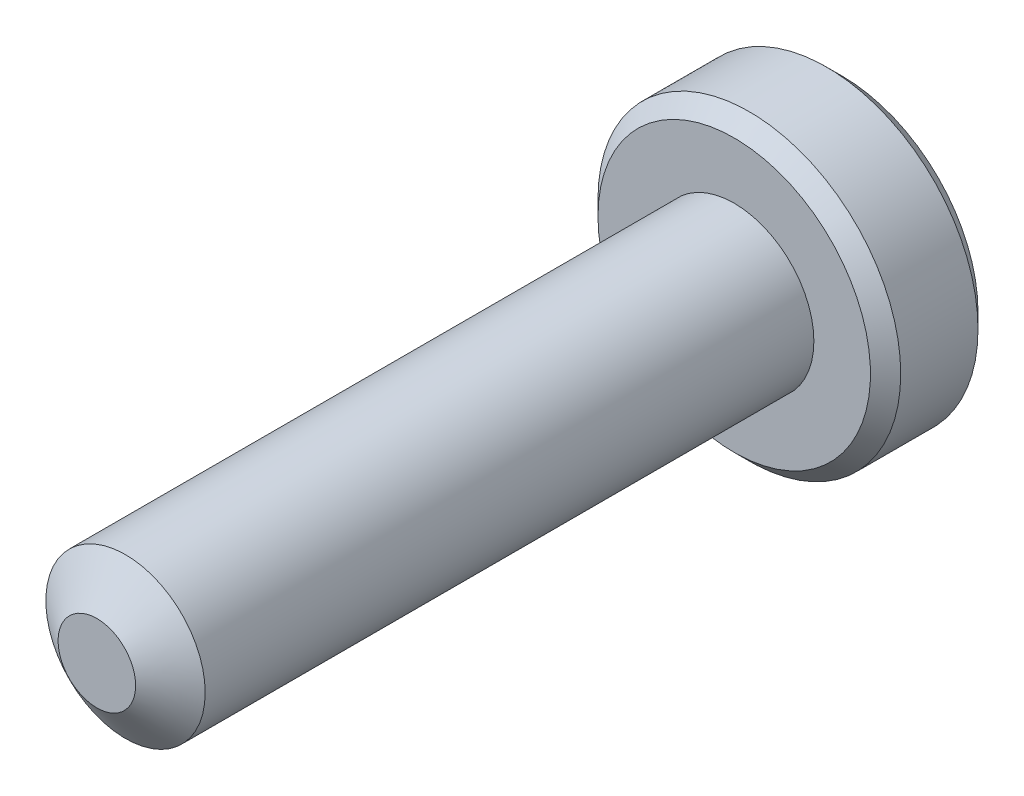
SolidWorks part; units mm, degrees
other "DetailItem1"
material "AISI 316 Stainless Steel Sheet (SS)"
ref_plane "Front Plane" through (0, 0, 0) normal (0, 0, 1) x (1, 0, 0)
ref_plane "Top Plane" through (0, 0, 0) normal (0, 1, 0) x (1, 0, 0)
ref_plane "Right Plane" through (0, 0, 0) normal (1, 0, 0) x (0, 0, -1)
sketch "Sketch1" plane through (0, 0, 0) normal (0, 0, 1) x (1, 0, 0)
  circle A0 centre (0, 0) radius 1
  dimension "OD" = 2
extrude "Extrude1" add sketch "Sketch1" against normal blind 8
sketch "Sketch2" plane through (0, 0, 0) normal (0, 0, 1) x (1, 0, 0)
  circle A0 centre (0, 0) radius 1 construction
  circle A1 centre (0, 0) radius 1
curve "Helix/Spiral1" [suppressed] pitch 0.4 height 8.4 turns 21 parameters "pitch"=0.4
sketch "Sketch3" plane through (0, 0, 0) normal (1, 0, 0) x (0, 0, -1)
  line L0 (-0.35, 1) -> (-0.2, 0.7402)
  line L1 (-0.2, 0.7402) -> (-0.15, 0.7402)
  line L2 (-0.15, 0.7402) -> (0, 1)
  line L3 (-0.35, 1) -> (0, 1)
  line L4 (-0.175, 1) -> (-0.175, 0.7402) construction
  line L5 (-0.275, 0.8701) -> (-0.075, 0.8701) construction
  line L6 (0, 1) -> (0, -1) construction
  dimension "D1" = 0.05
  dimension "D2" = 0.2
  dimension "D3" = 60
sweep "Cut-Sweep1" [suppressed] cut profiles "Sketch3" path "Helix/Spiral1"
sketch "Sketch4" plane through (0, 0, 0) normal (1, 0, 0) x (0, 0, -1)
  line L0 (0.3598, 1) -> (0, 0.4862)
  line L1 (0, 0.4862) -> (0, 1)
  line L2 (0.3598, 1) -> (0, 1)
  line L3 (-0.35, 1) -> (0, 1) construction
  line L4 (0, 0) -> (7.0209, 0) construction
  dimension "D1" = 55
  dimension "D2" = 0.254
revolve "Cut-Revolve1" cut sketch "Sketch4" angle 360 about L4
sketch "Sketch6" plane through (0, 0, -8) normal (0, 0, -1) x (-1, 0, 0)
  circle A0 centre (0, 0) radius 1.9
  dimension "head dia" = 3.8
extrude "Extrude2" add sketch "Sketch6" along normal blind 1.35
sketch "Sketch7" plane through (0, 0, -9.35) normal (0, 0, -1) x (-1, 0, 0)
  line L1 (0, 0.7506) -> (-0.65, 0.3753)
  line L2 (-0.65, 0.3753) -> (-0.65, -0.3753)
  line L3 (-0.65, -0.3753) -> (0, -0.7506)
  line L4 (0, -0.7506) -> (0.65, -0.3753)
  line L5 (0.65, -0.3753) -> (0.65, 0.3753)
  line L6 (0.65, 0.3753) -> (0, 0.7506)
  circle A0 centre (0, 0) radius 0.65 construction
  dimension "hex dia" = 1.3
extrude "Cut-Extrude1" cut sketch "Sketch7" against normal blind 0.975
sketch "Sketch8" plane through (0, 0, -9.35) normal (0, 0, -1) x (-1, 0, 0)
  circle A0 centre (0, 0) radius 0.7506
extrude "Cut-Extrude2" cut sketch "Sketch8" against normal through all draft 45
chamfer "Chamfer1" distance 0.19 angle 45 2 edges at (-1.9, 0, -9.35) (-1.9, 0, -8)
sketch "Sketch10" plane through (0, 0, -8) normal (0, 0, 1) x (1, 0, 0)
  circle A1 centre (0, 0) radius 1
  circle A2 centre (0, 0) radius 1
  dimension "D1" = 0
ref_plane "Plane1" through (0, 0, -30) normal (0, 0, 1) x (1, 0, 0)
extrude "partial thread" [suppressed] add sketch "Sketch10" along normal up to surface (10 mm away) separate body
chamfer "Chamfer2" [suppressed] distance 0.04 angle 45
combine bodies "Combine1" [suppressed] operation type add bodies to combine 107 108
sketch "Sketch9" plane through (0, 0, 0) normal (1, 0, 0) x (0, 0, -1)
  line L0 (0, 1) -> (0, -1) construction
  line L1 (1, 1) -> (1, -1) construction
  dimension "D1" = 1
equation "\"D3@Helix/Spiral1\" = \"screw length@Extrude1\"+\"pitch@Helix/Spiral1\""
equation "\"D1@Sketch3\" = \"pitch@Helix/Spiral1\"*.125"
equation "\"D2@Sketch3\" = \"pitch@Helix/Spiral1\"*.5"
equation "\"D1@Cut-Extrude1\" = \"hex dia@Sketch7\"*.75"
equation "\"D1@Chamfer1\" = \"head dia@Sketch6\"*.05"
equation "\"D1@Sketch9\" = \"pitch@Helix/Spiral1\"*2.5"
equation "\"D1@Chamfer2\"=\"OD@Sketch1\"*.02"
